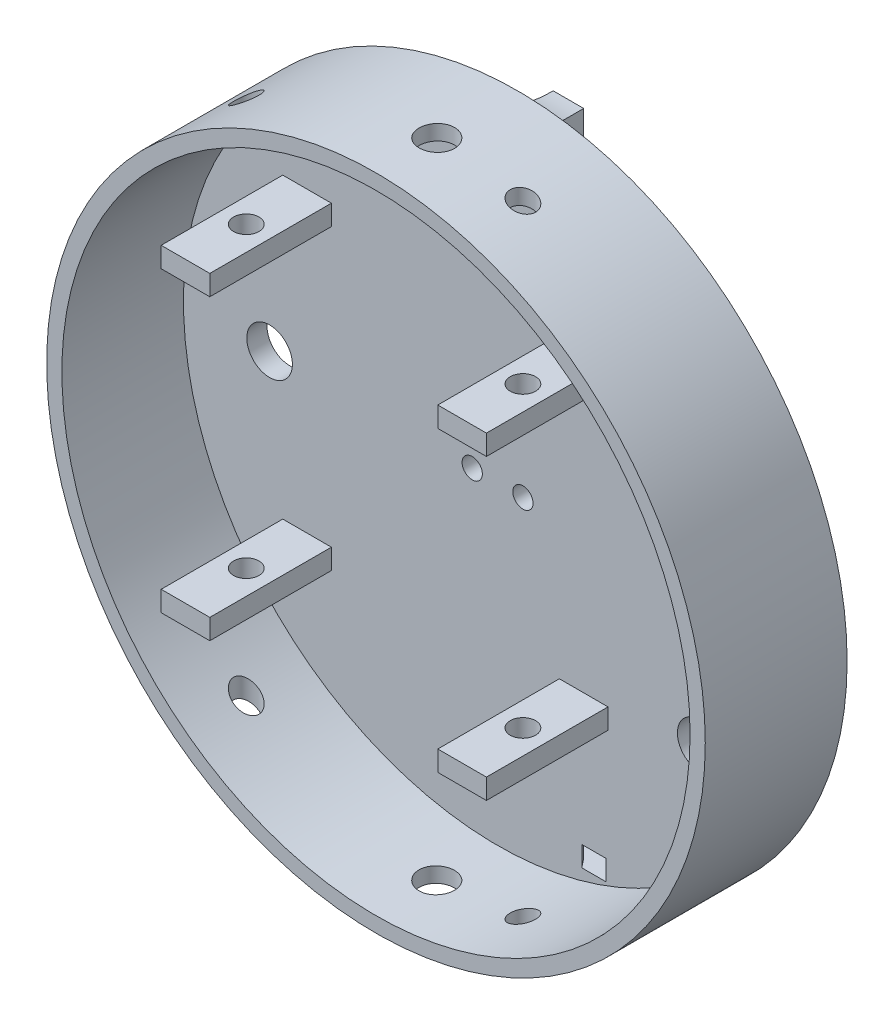
SolidWorks part; units mm, degrees
ref_plane "Alzado" through (0, 0, 0) normal (0, 0, 1) x (1, 0, 0)
ref_plane "Planta" through (0, 0, 0) normal (0, 1, 0) x (1, 0, 0)
ref_plane "Vista lateral" through (0, 0, 0) normal (1, 0, 0) x (0, 0, -1)
sketch "Croquis1" plane through (0, 0, 0) normal (0, 0, 1) x (1, 0, 0)
  line L0 (10, 20) -> (-10, 20) construction
  circle A0 centre (0, 0) radius 32.5
  circle A1 centre (-2.5, 0) radius 1
  circle A2 centre (2.5, 0) radius 1
  circle A3 centre (0, 20) radius 1
  circle A4 centre (10, 20) radius 1
  circle A5 centre (-10, 20) radius 1
  point P9 (0, 20)
  dimension "D1" = 65
  dimension "D4" = 2
  dimension "D7" = 2
  dimension "D2" = 2.5
  dimension "D3" = 2.5
  dimension "D5" = 20
  dimension "D6" = 20
extrude "Saliente-Extruir1" add sketch "Croquis1" along normal blind 2
sketch "Croquis2" plane through (0, 0, 2) normal (0, 0, 1) x (1, 0, 0)
  line L0 (-21.2, -15.7) -> (-16.4, -15.7)
  line L1 (10.9, -15.7) -> (6.1, -15.7)
  line L2 (-21.2, -15.7) -> (-21.2, -13.7)
  line L3 (-21.2, -13.7) -> (-16.4, -13.7)
  line L4 (-16.4, -13.7) -> (-16.4, -15.7)
  line L5 (6.1, -15.7) -> (6.1, -13.7)
  line L6 (6.1, -13.7) -> (10.9, -13.7)
  line L7 (10.9, -13.7) -> (10.9, -15.7)
  line L8 (6.1, -15.7) -> (10.9, -15.7)
  line L9 (0, 0) -> (12.8027, 0) construction
  line L10 (10.9, 13.7) -> (10.9, 15.7)
  line L11 (10.9, 15.7) -> (6.1, 15.7)
  line L12 (6.1, 13.7) -> (10.9, 13.7)
  line L13 (6.1, 15.7) -> (6.1, 13.7)
  line L14 (-16.4, 13.7) -> (-16.4, 15.7)
  line L15 (-21.2, 15.7) -> (-16.4, 15.7)
  line L16 (-21.2, 15.7) -> (-21.2, 13.7)
  line L17 (-21.2, 13.7) -> (-16.4, 13.7)
  point P2 (0, -15.7)
  point P3 (-16.4, -15.7)
  point P13 (8.5, -15.7)
  point P16 (8.5, 15.7)
  dimension "D1" = 32.1
  dimension "D2" = 10.9
  dimension "D3" = 15.7
  dimension "D4" = 4.8
  dimension "D5" = 4.8
  dimension "D6" = 2
  dimension "D7" = 2
extrude "Saliente-Extruir2" add sketch "Croquis2" along normal blind 12 contours L7 L6 L5 L1 | L4 L3 L2 L0 | L16 L17 L14 L15 | L11 L13 L12 L10 region at (-18.8, -14.7, 2) region at (8.5, -14.7, 2) region at (8.5, 14.7, 2) region at (-18.8, 14.7, 2)
sketch "Croquis3" plane through (0, -15.7, 0) normal (0, -1, 0) x (1, 0, 0)
  line L0 (-18.8, 14) -> (-18.8, 2) construction
  line L1 (-21.2, 14) -> (-16.4, 14) construction
  line L2 (-21.2, 2) -> (-16.4, 2) construction
  line L3 (8.5, 14) -> (8.5, 2) construction
  line L4 (10.9, 14) -> (6.1, 14) construction
  line L5 (10.9, 2) -> (6.1, 2) construction
  circle A0 centre (-18.8, 8) radius 1.25
  circle A1 centre (8.5, 8) radius 1.25
  dimension "D1" = 2.5
extrude "Cortar-Extruir1" cut sketch "Croquis3" against normal up to surface (31.4 mm away) up to face at (8.5, 15.7, 8)
ref_plane "Plano1" through (0, -32.5, 0) normal (0, -1, 0) x (-1, 0, 0)
ref_plane "Plano2" through (0, -28.75, 0) normal (0, -1, 0) x (-1, 0, 0)
sketch "Croquis5" plane through (0, -28.75, 0) normal (0, -1, 0) x (-1, 0, 0)
  line L0 (-8.5, -8) -> (18.8, -8) construction
  line L1 (0, 0) -> (0, -8) construction
  line L2 (-32.5, -2) -> (32.5, -2) construction
  line L3 (-10.68, -2) -> (-8.3104, -2)
  line L4 (32.5, 0) -> (-32.5, 0) construction
  line L5 (9.277, 0) -> (6.408, 0)
  line L6 (8.3104, -2) -> (10.68, -2)
  line L7 (-6.408, 0) -> (-9.277, 0)
  arc A0 (-9.277, 0) -> (-10.68, -2) centre (0, -8) ccw
  arc A1 (-6.408, 0) -> (-8.3104, -2) centre (0, -8) ccw
  arc A2 (10.68, -2) -> (9.277, 0) centre (0, -8) ccw
  arc A3 (8.3104, -2) -> (6.408, 0) centre (0, -8) ccw
  dimension "D1" = 24.5
  dimension "D2" = 20.5
extrude "Cortar-Extruir3" cut sketch "Croquis5" against normal blind 2
mirror "Simetría1" about plane through (0, 0, 0) normal (0, 1, 0) of "Cortar-Extruir3"
sketch "Croquis6" plane through (0, 0, 0) normal (0, 0, -1) x (-1, 0, 0)
  circle A0 centre (-20, 12.5) radius 2.25
  circle A1 centre (-20, -12.5) radius 2.25
  circle A2 centre (22.5, 0) radius 2.25
  dimension "D1" = 4.5
  dimension "D2" = 4.5
  dimension "D3" = 4.5
  dimension "D6" = 25
  dimension "D7" = 12.5
  dimension "D4" = 22.5
  dimension "D5" = 20
extrude "Cortar-Extruir4" cut sketch "Croquis6" against normal blind 2.5
sketch "Croquis7" plane through (0, 0, 2) normal (0, 0, 1) x (1, 0, 0)
  circle A2 centre (0, 0) radius 32.5 construction
  circle A9 centre (0, 0) radius 32.5
  circle A11 centre (0, 0) radius 31
  dimension "D1" = 1.5
extrude "Saliente-Extruir3" add sketch "Croquis7" along normal blind 12
ref_plane "Plano3" through (0, -32.5, 0) normal (0, -1, 0) x (-1, 0, 0)
sketch "Croquis8" plane through (0, -32.5, 0) normal (0, -1, 0) x (-1, 0, 0)
  circle A0 centre (-8.5, -8) radius 1.25 construction
  circle A1 centre (-8.5, -8) radius 1.25
  circle A2 centre (18.8, -8) radius 1.25 construction
  circle A3 centre (18.8, -8) radius 1.25
  circle A4 centre (0, -8) radius 1.75
  dimension "D1" = 3.5
extrude "Cortar-Extruir5" cut sketch "Croquis8" against normal blind 70
sketch "Sketch1" plane through (0, 0, 0) normal (0, 0, -1) x (-1, 0, 0)
  line L0 (6.408, 26.75) -> (6.408, 28.75) construction
  line L1 (-1.502, 29.25) -> (1.498, 29.25)
  line L2 (-1.502, 29.25) -> (-1.502, 26.25)
  line L3 (-1.502, 26.25) -> (1.498, 26.25)
  line L4 (1.498, 29.25) -> (1.498, 26.25)
  line L5 (-1.502, 29.25) -> (1.498, 26.25) construction
  line L6 (-1.502, 26.25) -> (1.498, 29.25) construction
  line L7 (0, 0) -> (-11.4103, 0) construction
  line L8 (-1.502, -26.25) -> (1.498, -29.25) construction
  line L9 (-1.502, -29.25) -> (1.498, -26.25) construction
  line L10 (1.498, -29.25) -> (1.498, -26.25)
  line L11 (-1.502, -26.25) -> (1.498, -26.25)
  line L12 (-1.502, -29.25) -> (-1.502, -26.25)
  line L13 (-1.502, -29.25) -> (1.498, -29.25)
  line L14 (-6.408, -26.75) -> (-6.408, -28.75) construction
  point P0 (-0.002, 27.75)
  point P8 (6.408, 27.75)
  point P15 (-0.002, -27.75)
  dimension "D1" = 4.91
  dimension "D2" = 3
  dimension "D3" = 3
  dimension "D4" = 4.906
extrude "Boss-Extrude1" add sketch "Sketch1" along normal blind 5
fillet "Fillet1" radius 2 6 edges at (1.502, 27.75, 0) (-1.498, -27.75, 0) (0.002, 26.25, 0) (0.002, 29.25, 0) (0.002, -26.25, 0) (0.002, -29.25, 0) second distance 5 first distance on face at (0.002, 27.75, 0)
sketch "Sketch2" plane through (0, 0, 2) normal (0, 0, 1) x (1, 0, 0)
  line L1 (-10.68, -26.75) -> (-5.6668, -26.75)
  line L2 (-10.68, -26.75) -> (-10.68, -28.75)
  line L3 (-10.68, -28.75) -> (-5.6668, -28.75)
  line L4 (-5.6668, -26.75) -> (-5.6668, -28.75)
  line L5 (10.68, 26.75) -> (5.4941, 26.75)
  line L6 (10.68, 26.75) -> (10.68, 28.75)
  line L7 (10.68, 28.75) -> (5.4941, 28.75)
  line L8 (5.4941, 26.75) -> (5.4941, 28.75)
extrude "Tapon" add sketch "Sketch2" against normal up to surface (2 mm away) up to face at (1.002, 26, 0)
equation "\"D2@Croquis6\"=\"D1@Croquis6\""
equation "\"D3@Croquis6\"=\"D1@Croquis6\""
equation "\"D7@Croquis6\"=\"D6@Croquis6\"/2"
